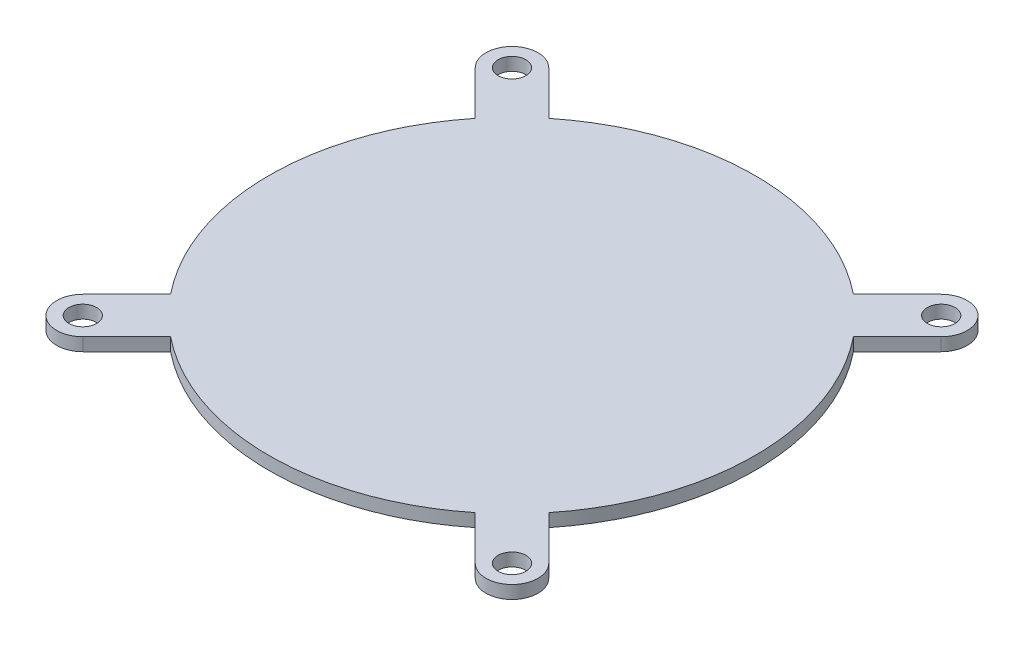
SolidWorks part; units mm, degrees
ref_plane "Front Plane" through (0, 0, 0) normal (0, 0, 1) x (1, 0, 0)
ref_plane "Top Plane" through (0, 0, 0) normal (0, 1, 0) x (1, 0, 0)
ref_plane "Right Plane" through (0, 0, 0) normal (1, 0, 0) x (0, 0, -1)
sketch "Sketch1" plane through (0, 0, 0) normal (0, 1, 0) x (1, 0, 0)
  line L5 (-23.3345, -19.0919) -> (-20.3833, -16.1407)
  line L7 (-19.0919, -23.3345) -> (-16.1407, -20.3833)
  line L9 (-23.3345, 19.0919) -> (-20.3833, 16.1407)
  line L11 (-19.0919, 23.3345) -> (-16.1407, 20.3833)
  line L13 (19.0919, 23.3345) -> (16.1407, 20.3833)
  line L15 (23.3345, 19.0919) -> (20.3833, 16.1407)
  line L17 (23.3345, -19.0919) -> (20.3833, -16.1407)
  line L19 (19.0919, -23.3345) -> (16.1407, -20.3833)
  arc A0 (20.3833, -16.1407) -> (20.3833, 16.1407) centre (0, 0) ccw
  circle A1 centre (-21.2132, 21.2132) radius 1.6
  arc A2 (-19.0919, 23.3345) -> (-23.3345, 19.0919) centre (-21.2132, 21.2132) ccw
  circle A3 centre (21.2132, 21.2132) radius 1.6
  arc A4 (23.3345, 19.0919) -> (19.0919, 23.3345) centre (21.2132, 21.2132) ccw
  circle A5 centre (-21.2132, -21.2132) radius 1.6
  arc A6 (-23.3345, -19.0919) -> (-19.0919, -23.3345) centre (-21.2132, -21.2132) ccw
  circle A7 centre (21.2132, -21.2132) radius 1.6
  arc A8 (19.0919, -23.3345) -> (23.3345, -19.0919) centre (21.2132, -21.2132) ccw
  arc A9 (-16.1407, -20.3833) -> (16.1407, -20.3833) centre (0, 0) ccw
  arc A10 (-20.3833, 16.1407) -> (-20.3833, -16.1407) centre (0, 0) ccw
  arc A11 (16.1407, 20.3833) -> (-16.1407, 20.3833) centre (0, 0) ccw
extrude "Boss-Extrude1" add sketch "Sketch1" along normal blind 1.5
fillet "Fillet1" radius 2 7 edges at (-20.3833, 0.75, -16.1407) (-16.1407, 0.75, -20.3833) (16.1407, 0.75, -20.3833) (20.3833, 0.75, -16.1407) (20.3833, 0.75, 16.1407) (16.1407, 0.75, 20.3833) (-16.1407, 0.75, 20.3833)
sketch "Sketch2" plane through (0, 0, 0) normal (0, -1, 0) x (-1, 0, 0)
  circle A0 centre (0, 0) radius 4
extrude "Boss-Extrude2" add sketch "Sketch2" along normal blind 5
sketch "Sketch3" plane through (0, 1.5, 0) normal (0, 1, 0) x (1, 0, 0)
  line L2 (-26.8701, 22.6274) -> (-19.9147, 15.6721)
  line L3 (15.6721, 19.9147) -> (19.9147, 15.6721)
  line L4 (-22.6274, 26.8701) -> (-15.6721, 19.9147)
  line L5 (-15.6721, 19.9147) -> (-19.9147, 15.6721)
  line L6 (22.6274, 26.8701) -> (15.6721, 19.9147)
  line L7 (26.8701, 22.6274) -> (19.9147, 15.6721)
  line L8 (26.8701, -22.6274) -> (19.9147, -15.6721)
  line L9 (22.6274, -26.8701) -> (15.6721, -19.9147)
  line L10 (-15.6721, -19.9147) -> (-19.9147, -15.6721)
  line L11 (-22.6274, -26.8701) -> (-15.6721, -19.9147)
  line L12 (15.6721, -19.9147) -> (19.9147, -15.6721)
  line L13 (-26.8701, -22.6274) -> (-19.9147, -15.6721)
  circle A0 centre (-24.7487, 24.7487) radius 1.6
  arc A1 (-22.6274, 26.8701) -> (-26.8701, 22.6274) centre (-24.7487, 24.7487) ccw
  arc A2 (22.6274, 26.8701) -> (26.8701, 22.6274) centre (24.7487, 24.7487) cw
  circle A3 centre (24.7487, 24.7487) radius 1.6
  circle A4 centre (24.7487, -24.7487) radius 1.6
  arc A5 (22.6274, -26.8701) -> (26.8701, -22.6274) centre (24.7487, -24.7487) ccw
  arc A6 (-22.6274, -26.8701) -> (-26.8701, -22.6274) centre (-24.7487, -24.7487) cw
  circle A7 centre (-24.7487, -24.7487) radius 1.6
sketch "Sketch5" plane through (0, -5, 0) normal (0, -1, 0) x (-1, 0, 0)
  circle A0 centre (0, 0) radius 13.8
extrude "Boss-Extrude4" add sketch "Sketch5" against normal up to surface (5 mm away) and the other way blind 3 up to face at (0, 0, 4)
sketch "Sketch6" plane through (0, -8, 0) normal (0, -1, 0) x (-1, 0, 0)
  circle A0 centre (0, 0) radius 10
extrude "Cut-Extrude2" cut sketch "Sketch6" against normal up to surface (8 mm away) up to face at (0, 0, 13.8)
extrude "Boss-Extrude5" add sketch "Sketch3" against normal up to surface (1.5 mm away) up to face at (0, 0, 13.8)
sketch "Sketch7" plane through (0, -8, 0) normal (0, -1, 0) x (-1, 0, 0)
  circle A0 centre (0, 0) radius 13.8
  circle A1 centre (0, 0) radius 10
extrude "Boss-Extrude6" add sketch "Sketch7" along normal blind 5
sketch "Sketch8" plane through (0, -13, 0) normal (0, -1, 0) x (-1, 0, 0)
  circle A0 centre (0, 0) radius 13.8
extrude "Cut-Extrude3" cut sketch "Sketch8" against normal blind 3
sketch "Sketch9" plane through (0, -10, 0) normal (0, -1, 0) x (-1, 0, 0)
  circle A0 centre (0, 0) radius 13.8
extrude "Cut-Extrude4" cut sketch "Sketch9" against normal blind 1
sketch "Sketch10" plane through (0, 1.5, 0) normal (0, 1, 0) x (1, 0, 0)
  circle A0 centre (0, 0) radius 28
extrude "Boss-Extrude7" add sketch "Sketch10" against normal up to surface (1.5 mm away) up to face at (0, 0, 13.8)
